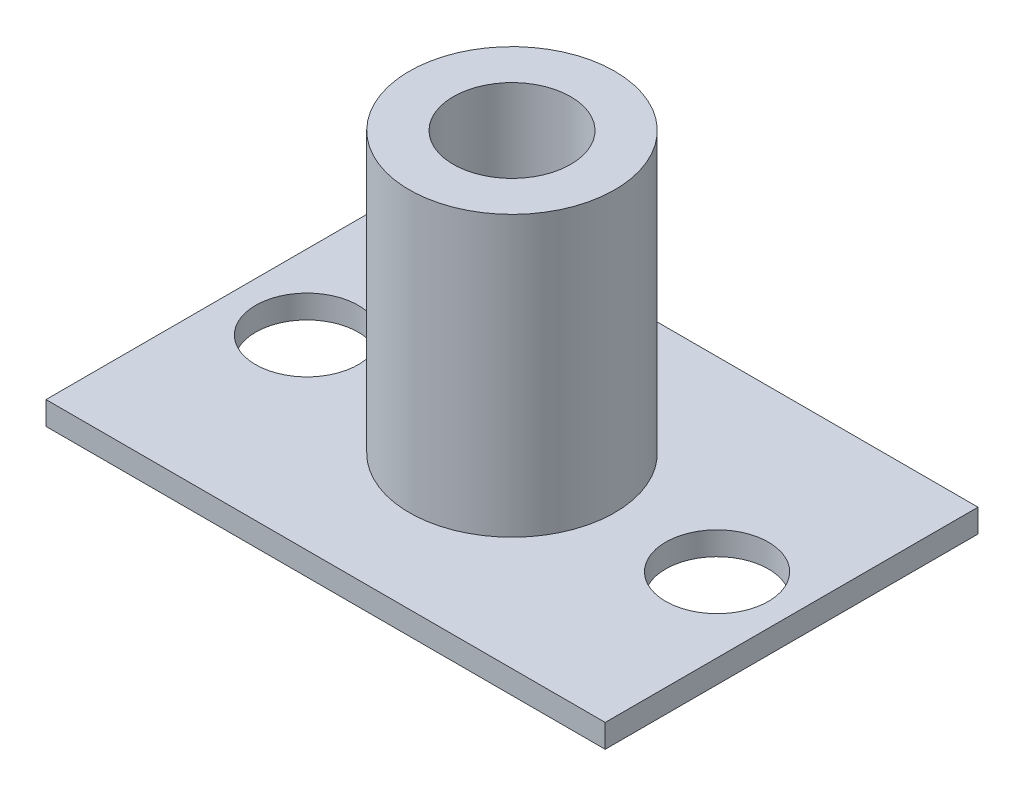
SolidWorks part; units mm, degrees
ref_plane "前视" through (0, 0, 0) normal (0, 0, 1) x (1, 0, 0)
ref_plane "上视" through (0, 0, 0) normal (0, 1, 0) x (1, 0, 0)
ref_plane "右视" through (0, 0, 0) normal (1, 0, 0) x (0, 0, -1)
sketch "Sketch1" plane through (0, 0, 0) normal (0, 1, 0) x (1, 0, 0)
  line L1 (-25.8417, 12.7) -> (12.2583, 12.7)
  line L2 (-25.8417, 12.7) -> (-25.8417, -12.7)
  line L3 (-25.8417, -12.7) -> (12.2583, -12.7)
  line L4 (12.2583, 12.7) -> (12.2583, -12.7)
  dimension "D1" = 25.4
  dimension "D2" = 38.1
extrude "Boss-Extrude1" add sketch "Sketch1" along normal blind 1.5875
ref_point "Point1"
sketch "Sketch3" plane through (0, 1.5875, 0) normal (0, 1, 0) x (1, 0, 0)
  circle A0 centre (-6.7917, 0) radius 7
  circle A1 centre (-6.7917, 0) radius 4
extrude "Boss-Extrude2" add sketch "Sketch3" along normal blind 19.05
ref_axis "Axis1" through (12.2583, 1.5875, 0) along (-1, 0, 0)
sketch "Sketch4" plane through (0, 1.5875, 0) normal (0, 1, 0) x (1, 0, 0)
  line L0 (12.2583, -12.7) -> (12.2583, 12.7) construction
  line L1 (-25.8417, 12.7) -> (-25.8417, -12.7) construction
  circle A0 centre (7.1783, 0) radius 3.5
  circle A1 centre (-20.7617, 0) radius 3.5
  point P0 (7.1783, 0)
  point P1 (12.2583, 0)
  point P4 (-20.7617, 0)
  dimension "D3" = 7
  dimension "D4" = 7
  dimension "D1" = 5.08
  dimension "D2" = 5.08
extrude "Cut-Extrude1" cut sketch "Sketch4" against normal through all
